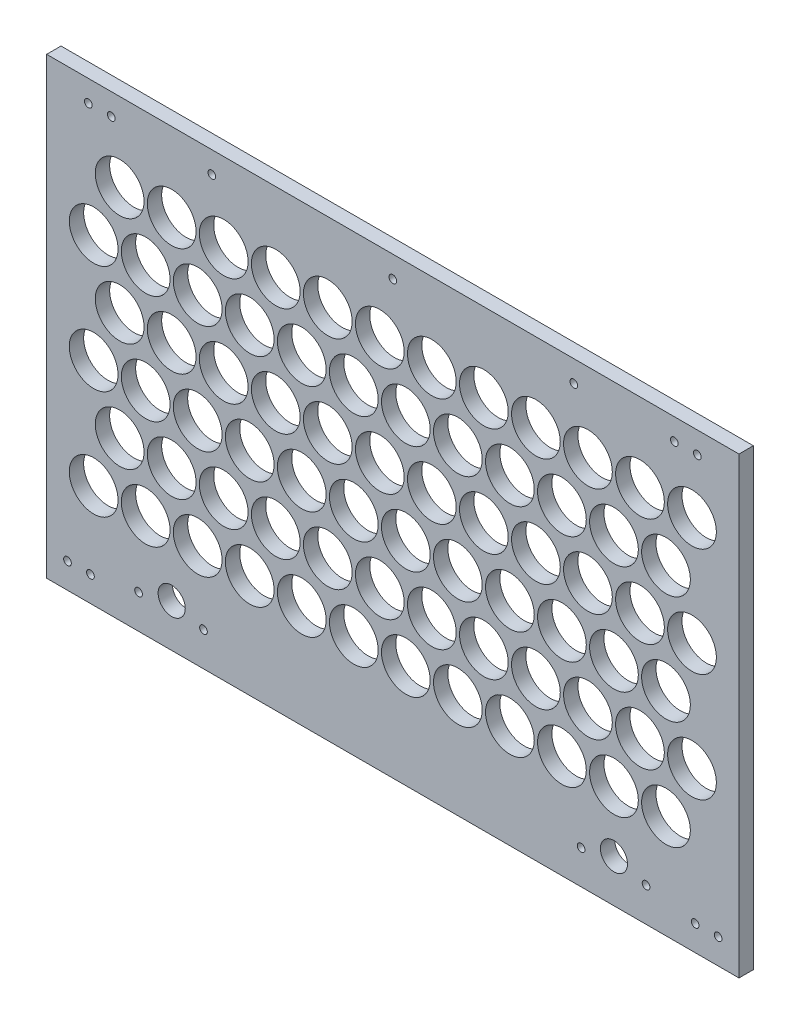
SolidWorks part; units mm, degrees
material "ABS"
ref_plane "X-Y Datum" through (0, 0, 0) normal (0, 0, 1) x (1, 0, 0)
ref_plane "X-Z Datum" through (0, 0, 0) normal (0, 1, 0) x (1, 0, 0)
ref_plane "Y-Z Datum" through (0, 0, 0) normal (1, 0, 0) x (0, 0, -1)
sketch "Sketch1" plane through (0, 0, 0) normal (0, 0, 1) x (1, 0, 0)
  line L1 (-143.025, 70.775) -> (143.025, 70.775)
  line L2 (-143.025, 70.775) -> (-143.025, -70.775)
  line L3 (-143.025, -70.775) -> (143.025, -70.775)
  line L4 (143.025, 70.775) -> (143.025, -70.775)
  line L5 (-143.025, 70.775) -> (143.025, -70.775) construction
  line L6 (-143.025, -70.775) -> (143.025, 70.775) construction
  line L13 (-153.025, -105.775) -> (153.025, -105.775)
  line L14 (-153.025, 91.65) -> (153.025, 91.65)
  line L15 (-153.025, 91.65) -> (-153.025, -105.775)
  line L16 (153.025, 91.65) -> (153.025, -105.775)
  line L17 (153.025, 70.775) -> (153.025, -70.775) construction
  line L18 (-143.025, 91.65) -> (143.025, 91.65) construction
  line L19 (-143.025, -105.775) -> (143.025, -105.775) construction
  line L20 (-153.025, 70.775) -> (-153.025, -70.775) construction
  line L21 (-132.25, -60) -> (-109.25, -60) construction
  circle A0 centre (-132.25, -60) radius 10.775
  circle A1 centre (-109.25, -60) radius 10.775 construction
  circle A2 centre (-120.75, -36) radius 10.775
  point P0 (0, 0)
  point P16 (-120.75, -60)
  dimension "D1" = 21.55
  dimension "D2" = 23
  dimension "D3" = 24
  dimension "D5" = 141.55
  dimension "D6" = 286.05
  dimension "D7" = 35
  dimension "D8" = 20.875
  dimension "D9" = 10
  dimension "D10" = 10
extrude "Boss-Extrude1" add sketch "Sketch1" along normal blind 6.35 contours A0 L3 L4 L1 L2 A2 | A2 | A0 | A0 L2 L3 | L1 L4 L3 L2 region at (2.4105, 0.9241, 0) region at (-140.6182, -68.3682, 0) region at (-132.25, -60, 0) region at (-149.383, -7.0625, 0) region at (-120.75, -36, 0)
sketch "Sketch3" plane through (0, 0, 6.35) normal (0, 0, 1) x (1, 0, 0)
  line L4 (143.025, 70.775) -> (-143.025, 70.775)
  line L5 (143.025, -70.775) -> (143.025, 70.775)
  line L6 (-143.025, -70.775) -> (143.025, -70.775)
  line L7 (-143.025, 70.775) -> (-143.025, -70.775)
  line L8 (143.025, 70.775) -> (-143.025, 70.775)
  line L9 (143.025, -70.775) -> (143.025, 70.775)
  line L10 (-143.025, -70.775) -> (143.025, -70.775)
  line L11 (-143.025, 70.775) -> (-143.025, -70.775)
  circle A1 centre (-120.75, -36) radius 10.775
  circle A2 centre (-120.75, -36) radius 10.775
  circle A3 centre (-132.25, -60) radius 10.775
  circle A4 centre (-132.25, -60) radius 10.775
  dimension "D1" = 0
  dimension "D2" = 0
  dimension "D3" = 0
extrude "Cut-Extrude1" cut sketch "Sketch3" against normal through all contours A4 region at (-132.25, -60, 6.35)
sketch "Sketch4" plane through (0, 0, 6.35) normal (0, 0, 1) x (1, 0, 0)
  line L4 (143.025, 70.775) -> (-143.025, 70.775)
  line L5 (143.025, -70.775) -> (143.025, 70.775)
  line L6 (-143.025, -70.775) -> (143.025, -70.775)
  line L7 (-143.025, 70.775) -> (-143.025, -70.775)
  line L8 (143.025, 70.775) -> (-143.025, 70.775)
  line L9 (143.025, -70.775) -> (143.025, 70.775)
  line L10 (-143.025, -70.775) -> (143.025, -70.775)
  line L11 (-143.025, 70.775) -> (-143.025, -70.775)
  circle A1 centre (-120.75, -36) radius 10.775
  circle A2 centre (-120.75, -36) radius 10.775
  circle A3 centre (-132.25, -60) radius 10.775
  circle A4 centre (-132.25, -60) radius 10.775
  dimension "D1" = 0
  dimension "D2" = 0
  dimension "D3" = 0
extrude "Cut-Extrude2" cut sketch "Sketch4" against normal through all contours A2 region at (-120.75, -36, 6.35)
pattern_linear "LPattern1" count 12 spacing 23 along (1, 0, 0) of "Cut-Extrude1", "Cut-Extrude2"
pattern_linear "LPattern2" count 3 spacing 48 along (0, 1, 0) of "LPattern1"
sketch "Sketch5" plane through (0, 0, 0) normal (0, 0, -1) x (-1, 0, 0)
sketch "Sketch13" plane through (0, 91.65, 0) normal (0, 1, 0) x (1, 0, 0)
  line L4 (153.025, 0) -> (-153.025, 0)
  line L5 (-153.025, 0) -> (-153.025, -6.35)
  line L6 (-153.025, -6.35) -> (153.025, -6.35)
  line L7 (153.025, -6.35) -> (153.025, 0)
  line L8 (153.025, 0) -> (-153.025, 0)
  line L9 (-153.025, 0) -> (-153.025, -6.35)
  line L10 (-153.025, -6.35) -> (153.025, -6.35)
  line L11 (153.025, -6.35) -> (153.025, 0)
  dimension "D1" = 0
extrude "Boss-Extrude2" add sketch "Sketch13" along normal blind 3.175
sketch "Sketch14" plane through (0, 0, 0) normal (0, 0, -1) x (-1, 0, 0)
  circle A0 centre (-97.75, -86.775) radius 6
extrude "Cut-Extrude3" cut sketch "Sketch14" against normal through all
mirror "Mirror1" about plane through (0, 0, 0) normal (1, 0, 0) of "Cut-Extrude3"
sketch "Sketch15" plane through (0, 0, 0) normal (0, 0, -1) x (-1, 0, 0)
  point P0 (-111.94, -90.775)
  point P1 (-83.25, -90.775)
  point P3 (83.712, -90.775)
  point P11 (80, 85.3)
  point P13 (0, 85.3)
  point P15 (-80, 85.3)
  point P41 (112.402, -90.775)
  point P47 (-143.8175, -94.6)
  point P50 (-133.6575, -94.6)
  point P54 (-134.61, 85.3)
  point P57 (-124.45, 85.3)
  point P61 (124.45, 85.3)
  point P64 (134.61, 85.3)
  point P68 (133.6575, -94.6)
  point P71 (143.8175, -94.6)
hole_wizard "M3 Clearance Hole1" positions "Sketch15" profile "Sketch16" hole size "M3" standard "ANSI Metric" end condition through all
sketch "Sketch16" plane through (111.94, -90.775, 0) normal (1, 0, 0) x (0, 1, 0)
  line L0 (0, 0) -> (0, 6.35)
  line L1 (0, 6.35) -> (1.7, 6.35)
  line L2 (1.7, 6.35) -> (1.7, 0)
  line L5 (1.7, 0) -> (0, 0)
  line L11 (0, -6.35) -> (0, 107.95) construction
  dimension "Thru Hole Dia." = 3.4
  dimension "Thru Hole Depth" = 6.35
sketch "Sketch17" plane through (0, 0, 0) normal (0, 0, -1) x (-1, 0, 0)
  line L0 (0, -105.775) -> (0, -77.9164) construction
  line L1 (153.025, -105.775) -> (-153.025, -105.775) construction
  circle A0 centre (0, -90.775) radius 2.25
  circle A1 centre (140.6875, 12) radius 2.25
  circle A2 centre (-140.6875, -12) radius 2.25
  point P0 (-140.6875, -12)
  point P1 (140.6875, 12)
  point P9 (0, -90.775)
  point P11 (83.712, -90.775)
  dimension "D1" = 4.5
extrude "Cut-Extrude4" [suppressed] cut sketch "Sketch17" against normal through all
